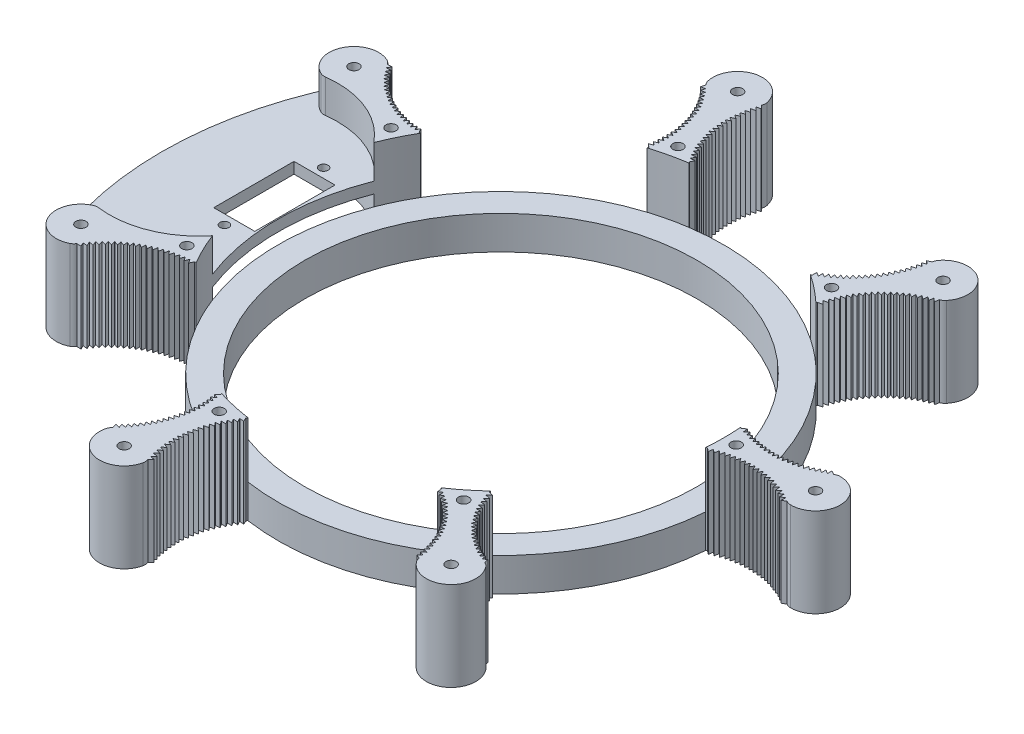
SolidWorks part; units mm, degrees
ref_plane "Front Plane" through (0, 0, 0) normal (0, 0, 1) x (1, 0, 0)
ref_plane "Top Plane" through (0, 0, 0) normal (0, 1, 0) x (1, 0, 0)
ref_plane "Right Plane" through (0, 0, 0) normal (1, 0, 0) x (0, 0, -1)
sketch "Sketch1" plane through (0, 0, 0) normal (0, 1, 0) x (1, 0, 0)
  circle A0 centre (0, 0) radius 63.5
  circle A1 centre (0, 0) radius 55.88
extrude "Boss-Extrude1" add sketch "Sketch1" along normal blind 9.525
sketch "Sketch2" plane through (0, 0, 0) normal (0, 1, 0) x (1, 0, 0)
  line L0 (0, 0) -> (143.528, 0) construction
  line L1 (0, 0) -> (106.3854, -8.3727) construction
  line L2 (88.1774, 6.6273) -> (87.0588, 7.2287)
  line L3 (87.0588, 7.2287) -> (87.0973, 5.9593)
  line L4 (87.0973, 5.9593) -> (88.1774, 6.6273) construction
  line L5 (87.086, 5.9526) -> (85.9991, 6.6097)
  line L6 (85.9991, 6.6097) -> (85.9735, 5.34)
  line L7 (85.9618, 5.3339) -> (84.9096, 6.045)
  line L8 (84.9096, 6.045) -> (84.8199, 4.7782)
  line L9 (84.8079, 4.7727) -> (83.7929, 5.5361)
  line L10 (83.7929, 5.5361) -> (83.6393, 4.2754)
  line L11 (83.6271, 4.2706) -> (82.652, 5.0842)
  line L12 (82.652, 5.0842) -> (82.4349, 3.8329)
  line L13 (82.4225, 3.8287) -> (81.4897, 4.6905)
  line L14 (81.4897, 4.6905) -> (81.2097, 3.4518)
  line L15 (81.197, 3.4482) -> (80.309, 4.356)
  line L16 (80.309, 4.356) -> (79.9668, 3.133)
  line L17 (79.954, 3.1301) -> (79.1129, 4.0816)
  line L18 (79.1129, 4.0816) -> (78.7094, 2.8774)
  line L19 (78.6964, 2.8751) -> (77.9044, 3.8679)
  line L20 (77.9044, 3.8679) -> (77.4406, 2.6856)
  line L21 (77.4276, 2.684) -> (76.6867, 3.7155)
  line L22 (76.6867, 3.7155) -> (76.1638, 2.5582)
  line L23 (76.1507, 2.5572) -> (75.4629, 3.6249)
  line L24 (75.4629, 3.6249) -> (74.8822, 2.4954)
  line L25 (74.8691, 2.4951) -> (74.2361, 3.5961)
  line L26 (74.2361, 3.5961) -> (73.5991, 2.4974)
  line L27 (73.586, 2.4977) -> (73.0094, 3.6293)
  line L28 (73.0094, 3.6293) -> (72.3177, 2.5642)
  line L29 (72.3046, 2.5652) -> (71.7859, 3.7244)
  line L30 (71.7859, 3.7244) -> (71.0413, 2.6956)
  line L31 (71.0283, 2.6973) -> (70.5688, 3.8812)
  line L32 (70.5688, 3.8812) -> (69.7732, 2.8913)
  line L33 (69.7602, 2.8936) -> (69.3611, 4.0993)
  line L34 (69.3611, 4.0993) -> (68.5165, 3.1508)
  line L35 (68.5037, 3.1538) -> (68.166, 4.3781)
  line L36 (68.166, 4.3781) -> (67.2746, 3.4734)
  line L37 (67.262, 3.4771) -> (66.9865, 4.7168)
  line L38 (66.9865, 4.7168) -> (66.0506, 3.8584)
  line L39 (66.0382, 3.8627) -> (65.8256, 5.1147)
  line L40 (65.8256, 5.1147) -> (64.8476, 4.3047)
  line L41 (64.8354, 4.3095) -> (64.6863, 5.5708)
  line L42 (64.6863, 5.5708) -> (63.6686, 4.8111)
  line L43 (88.1774, -6.6273) -> (87.0588, -7.2287)
  line L44 (87.0588, -7.2287) -> (87.0973, -5.9593)
  line L45 (87.086, -5.9526) -> (85.9991, -6.6097)
  line L46 (85.9991, -6.6097) -> (85.9735, -5.34)
  line L47 (85.9618, -5.3339) -> (84.9096, -6.045)
  line L48 (84.9096, -6.045) -> (84.8199, -4.7782)
  line L49 (84.8079, -4.7727) -> (83.7929, -5.5361)
  line L50 (83.7929, -5.5361) -> (83.6393, -4.2754)
  line L51 (83.6271, -4.2706) -> (82.652, -5.0842)
  line L52 (82.652, -5.0842) -> (82.4349, -3.8329)
  line L53 (82.4225, -3.8287) -> (81.4897, -4.6905)
  line L54 (81.4897, -4.6905) -> (81.2097, -3.4518)
  line L55 (81.197, -3.4482) -> (80.309, -4.356)
  line L56 (80.309, -4.356) -> (79.9668, -3.133)
  line L57 (79.954, -3.1301) -> (79.1129, -4.0816)
  line L58 (79.1129, -4.0816) -> (78.7094, -2.8774)
  line L59 (78.6964, -2.8751) -> (77.9044, -3.8679)
  line L60 (77.9044, -3.8679) -> (77.4406, -2.6856)
  line L61 (77.4276, -2.684) -> (76.6867, -3.7155)
  line L62 (76.6867, -3.7155) -> (76.1638, -2.5582)
  line L63 (76.1507, -2.5572) -> (75.4629, -3.6249)
  line L64 (75.4629, -3.6249) -> (74.8822, -2.4954)
  line L65 (74.8691, -2.4951) -> (74.2361, -3.5961)
  line L66 (74.2361, -3.5961) -> (73.5991, -2.4974)
  line L67 (73.586, -2.4977) -> (73.0094, -3.6293)
  line L68 (73.0094, -3.6293) -> (72.3177, -2.5642)
  line L69 (72.3046, -2.5652) -> (71.7859, -3.7244)
  line L70 (71.7859, -3.7244) -> (71.0413, -2.6956)
  line L71 (71.0283, -2.6973) -> (70.5688, -3.8812)
  line L72 (70.5688, -3.8812) -> (69.7732, -2.8913)
  line L73 (69.7602, -2.8936) -> (69.3611, -4.0993)
  line L74 (69.3611, -4.0993) -> (68.5165, -3.1508)
  line L75 (68.5037, -3.1538) -> (68.166, -4.3781)
  line L76 (68.166, -4.3781) -> (67.2746, -3.4734)
  line L77 (67.262, -3.4771) -> (66.9865, -4.7168)
  line L78 (66.9865, -4.7168) -> (66.0506, -3.8584)
  line L79 (66.0382, -3.8627) -> (65.8256, -5.1147)
  line L80 (65.8256, -5.1147) -> (64.8476, -4.3047)
  line L81 (64.8354, -4.3095) -> (64.6863, -5.5708)
  line L82 (64.6863, -5.5708) -> (63.6686, -4.8111)
  arc A0 (89.5346, -7.041) -> (89.5346, 7.041) centre (89.6247, 0) ccw
  arc A1 (63.3043, -4.9822) -> (88.1774, -6.6273) centre (74.2802, -27.8883) cw
  arc A2 (88.1774, 6.6273) -> (89.5346, 7.041) centre (89.5671, 4.5012) cw
  circle A3 centre (0, 0) radius 63.5 construction
  arc A4 (88.1774, -6.6273) -> (89.5346, -7.041) centre (89.5671, -4.5012) ccw
  arc A5 (63.3043, -4.9822) -> (63.2288, 5.8623) centre (0, 0) ccw
  arc A6 (63.3043, 4.9822) -> (88.1774, 6.6273) centre (74.2802, 27.8883) ccw
  circle A7 centre (89.6247, 0) radius 1.4605
  circle A8 centre (67.0187, 0) radius 1.4605
  point P13 (88.7043, -6.9812)
  point P84 (74.2802, 27.8883)
  dimension "D1" = 25.4
  dimension "D2" = 25.4
  dimension "D3" = 2.54
  dimension "D5" = 22.606
  dimension "D6" = 20
  dimension "D7" = 2.921
  dimension "D4" = 4.5
extrude "Boss-Extrude2" add sketch "Sketch2" along normal blind 25.4 contours A5 A6 A2 A0 A4 A1 region at (82.3063, 0, 0)
pattern_circular "CirPattern7" count 7 over 360 about axis through (0, 25.4, 0) along (0, -1, 0) of "Boss-Extrude2"
ref_plane "Plane1" through (0, 15.875, 0) normal (0, -1, 0) x (-1, 0, 0)
sketch "Sketch4" plane through (0, 15.875, 0) normal (0, -1, 0) x (-1, 0, 0)
  line L0 (0, 0) -> (125.7054, -60.5365) construction
  arc A7 (82.3206, 32.2877) -> (59.1968, 22.9779) centre (79.0244, 7.1025) ccw construction
  arc A14 (87.0934, 41.942) -> (87.0934, -41.942) centre (0, 0) cw
  arc A15 (83.7229, 32.5039) -> (77.6129, 45.1914) centre (80.7491, 38.8867) ccw construction
  arc A16 (82.3206, 32.2877) -> (83.7229, 32.5039) centre (82.6502, 34.8062) ccw construction
  arc A17 (59.1968, -22.9779) -> (59.1968, 22.9779) centre (0, 0) ccw construction
  arc A18 (59.1968, -22.9779) -> (82.3206, -32.2877) centre (79.0244, -7.1025) ccw construction
  arc A19 (77.6129, -45.1914) -> (83.7229, -32.5039) centre (80.7491, -38.8867) ccw construction
  arc A20 (83.7229, -32.5039) -> (82.3206, -32.2877) centre (82.6502, -34.8062) ccw construction
  arc A21 (82.3206, 32.2877) -> (59.1968, 22.9779) centre (79.0244, 7.1025) ccw
  arc A22 (83.7229, 32.5039) -> (87.0934, 41.942) centre (80.7491, 38.8867) ccw
  arc A23 (82.3206, 32.2877) -> (83.7229, 32.5039) centre (82.6502, 34.8062) ccw
  arc A24 (59.1968, -22.9779) -> (59.1968, 22.9779) centre (0, 0) ccw
  arc A25 (59.1968, -22.9779) -> (82.3206, -32.2877) centre (79.0244, -7.1025) ccw
  arc A26 (87.0934, -41.942) -> (83.7229, -32.5039) centre (80.7491, -38.8867) ccw
  arc A27 (83.7229, -32.5039) -> (82.3206, -32.2877) centre (82.6502, -34.8062) ccw
extrude "Boss-Extrude3" add sketch "Sketch4" along normal blind 3.175
sketch "Sketch5" plane through (0, 12.7, 0) normal (0, -1, 0) x (-1, 0, 0)
  line L0 (59.1968, -22.9779) -> (59.1968, 22.9779) construction
  line L1 (59.1968, 0) -> (63.7688, 0) construction
  line L2 (63.7688, 0) -> (63.7688, -6.35)
  line L3 (63.7688, -6.35) -> (75.4528, -6.35)
  line L4 (75.4528, -6.35) -> (75.4528, 16.51)
  line L5 (75.4528, 16.51) -> (63.7688, 16.51)
  line L6 (63.7688, 16.51) -> (63.7688, 0)
extrude "Cut-Extrude1" cut sketch "Sketch5" against normal through all
sketch "Sketch6" plane through (0, 12.7, 0) normal (0, -1, 0) x (1, 0, 0)
  circle A0 centre (-69.6743, -19.1516) radius 1.27
extrude "Cut-Extrude2" cut sketch "Sketch6" against normal up to surface (3.175 mm away) up to face at (-69.6108, 15.875, -5.08)
sketch "Sketch7" plane through (0, 12.7, 0) normal (0, -1, 0) x (1, 0, 0)
  circle A0 centre (-69.6743, 9.0932) radius 1.27
extrude "Cut-Extrude3" cut sketch "Sketch7" against normal up to surface (3.175 mm away) up to face at (-69.6743, 15.875, -20.4216)
extrude "Boss-Extrude4" add sketch "Sketch2<4>" along normal up to surface (25.4 mm away) contours A6 L42 L41 region at (64.3954, 0, -4.8939) up to face at (89.6247, 25.4, -1.4605)
sketch "Sketch2<4>" plane through (0, 0, 0) normal (0, 1, 0) x (1, 0, 0) same geometry as "Sketch2"
extrude "Boss-Extrude5" add sketch "Sketch2<5>" along normal up to surface (25.4 mm away) contours L82 A1 L81 region at (64.3954, 0, 4.8939) up to face at (89.6247, 25.4, -1.4605)
sketch "Sketch2<5>" plane through (0, 0, 0) normal (0, 1, 0) x (1, 0, 0) same geometry as "Sketch2"
pattern_circular "CirPattern2" count 20 over 55 about axis through (74.2802, 25.4, 27.8883) along (0, -1, 0) of "Boss-Extrude5"
pattern_circular "CirPattern3" count 20 over 55 about axis through (74.2802, 25.4, -27.8883) along (0, -1, 0) of "Boss-Extrude4" reverse direction yes
pattern_circular "CirPattern4" count 7 over 360 about axis through (0, 25.4, 0) along (0, -1, 0) skipping 4 of "CirPattern3"
pattern_circular "CirPattern5" count 7 over 360 about axis through (0, 9.525, 0) along (0, -1, 0) skipping 3 of "CirPattern2"
sketch "Sketch11" plane through (0, 15.875, 0) normal (0, 1, 0) x (1, 0, 0)
  line L0 (-55.276, 31.9594) -> (-55.8633, 33.0854) construction
  line L1 (-55.8633, 33.0854) -> (-56.5448, 32.0138) construction
  line L2 (-56.5448, 32.0138) -> (-56.5579, 32.0147) construction
  line L3 (-56.5579, 32.0147) -> (-57.0877, 33.1689) construction
  line L4 (-57.0877, 33.1689) -> (-57.8224, 32.133) construction
  line L5 (-57.8224, 32.133) -> (-57.8354, 32.1346) construction
  line L6 (-57.8354, 32.1346) -> (-58.3062, 33.3141) construction
  line L7 (-58.3062, 33.3141) -> (-59.0923, 32.3166) construction
  line L8 (-59.0923, 32.3166) -> (-59.1053, 32.3188) construction
  line L9 (-59.1053, 32.3188) -> (-59.5159, 33.5206) construction
  line L10 (-59.5159, 33.5206) -> (-60.3514, 32.5641) construction
  line L11 (-60.3514, 32.5641) -> (-60.3642, 32.567) construction
  line L12 (-60.3642, 32.567) -> (-60.7136, 33.788) construction
  line L13 (-60.7136, 33.788) -> (-61.5963, 32.8749) construction
  line L14 (-61.5963, 32.8749) -> (-61.609, 32.8784) construction
  line L15 (-61.609, 32.8784) -> (-61.8962, 34.1155) construction
  line L16 (-61.8962, 34.1155) -> (-62.8239, 33.2482) construction
  line L17 (-62.8239, 33.2482) -> (-62.8364, 33.2523) construction
  line L18 (-62.8364, 33.2523) -> (-63.0609, 34.5023) construction
  line L19 (-63.0609, 34.5023) -> (-64.0312, 33.6829) construction
  line L20 (-64.0312, 33.6829) -> (-64.0434, 33.6877) construction
  line L21 (-64.0434, 33.6877) -> (-64.2045, 34.9475) construction
  line L22 (-64.2045, 34.9475) -> (-65.2149, 34.1781) construction
  line L23 (-65.2149, 34.1781) -> (-65.2269, 34.1835) construction
  line L24 (-65.2269, 34.1835) -> (-65.3241, 35.4498) construction
  line L25 (-65.3241, 35.4498) -> (-66.3721, 34.7325) construction
  line L26 (-66.3721, 34.7325) -> (-66.3839, 34.7384) construction
  line L27 (-66.3839, 34.7384) -> (-66.417, 36.008) construction
  line L28 (-66.417, 36.008) -> (-67.4999, 35.3445) construction
  line L29 (-67.4999, 35.3445) -> (-67.5113, 35.3511) construction
  line L30 (-67.5113, 35.3511) -> (-67.4803, 36.6207) construction
  line L31 (-67.4803, 36.6207) -> (-68.5953, 36.0128) construction
  line L32 (-68.5953, 36.0128) -> (-68.6063, 36.0199) construction
  line L33 (-68.6063, 36.0199) -> (-68.5112, 37.2863) construction
  line L34 (-68.5112, 37.2863) -> (-69.6556, 36.7355) construction
  line L35 (-69.6556, 36.7355) -> (-69.6662, 36.7432) construction
  line L36 (-69.6662, 36.7432) -> (-69.5073, 38.0032) construction
  line L37 (-69.5073, 38.0032) -> (-70.678, 37.5108) construction
  line L38 (-70.678, 37.5108) -> (-70.6882, 37.519) construction
  line L39 (-70.6882, 37.519) -> (-70.4659, 38.7694) construction
  line L40 (-70.4659, 38.7694) -> (-71.6599, 38.3368) construction
  line L41 (-71.6599, 38.3368) -> (-71.6697, 38.3455) construction
  line L42 (-71.6697, 38.3455) -> (-71.3845, 39.5831) construction
  line L43 (-71.3845, 39.5831) -> (-72.5989, 39.2113) construction
  line L44 (-72.5989, 39.2113) -> (-72.6083, 39.2205) construction
  line L45 (-72.6083, 39.2205) -> (-72.2609, 40.4421) construction
  line L46 (-72.2609, 40.4421) -> (-73.4925, 40.1321) construction
  line L47 (-73.4925, 40.1321) -> (-73.5014, 40.1418) construction
  line L48 (-73.5014, 40.1418) -> (-73.0928, 41.3442) construction
  line L49 (-73.0928, 41.3442) -> (-74.3385, 41.0969) construction
  line L50 (-74.3385, 41.0969) -> (-74.3469, 41.107) construction
  line L51 (-74.3469, 41.107) -> (-73.8781, 42.2873) construction
  line L52 (-73.8781, 42.2873) -> (-75.1346, 42.1031) construction
  line L53 (-75.1346, 42.1031) -> (-75.1425, 42.1136) construction
  line L54 (-75.1425, 42.1136) -> (-74.6147, 43.2688) construction
  line L55 (-74.6147, 43.2688) -> (-75.879, 43.1483) construction
  line L56 (-75.879, 43.1483) -> (-75.8863, 43.1592) construction
  line L57 (-75.8863, 43.1592) -> (-75.3009, 44.2862) construction
  line L58 (-75.3009, 44.2862) -> (-76.5696, 44.2297) construction
  line L59 (-76.5696, -44.2297) -> (-75.3009, -44.2862) construction
  line L60 (-75.3009, -44.2862) -> (-75.8863, -43.1592) construction
  line L61 (-75.8863, -43.1592) -> (-75.879, -43.1483) construction
  line L62 (-75.879, -43.1483) -> (-74.6147, -43.2688) construction
  line L63 (-74.6147, -43.2688) -> (-75.1425, -42.1136) construction
  line L64 (-75.1425, -42.1136) -> (-75.1346, -42.1031) construction
  line L65 (-75.1346, -42.1031) -> (-73.8781, -42.2873) construction
  line L66 (-73.8781, -42.2873) -> (-74.3469, -41.107) construction
  line L67 (-74.3469, -41.107) -> (-74.3385, -41.0969) construction
  line L68 (-74.3385, -41.0969) -> (-73.0928, -41.3442) construction
  line L69 (-73.0928, -41.3442) -> (-73.5014, -40.1418) construction
  line L70 (-73.5014, -40.1418) -> (-73.4925, -40.1321) construction
  line L71 (-73.4925, -40.1321) -> (-72.2609, -40.4421) construction
  line L72 (-72.2609, -40.4421) -> (-72.6083, -39.2205) construction
  line L73 (-72.6083, -39.2205) -> (-72.5989, -39.2113) construction
  line L74 (-72.5989, -39.2113) -> (-71.3845, -39.5831) construction
  line L75 (-71.3845, -39.5831) -> (-71.6697, -38.3455) construction
  line L76 (-71.6697, -38.3455) -> (-71.6599, -38.3368) construction
  line L77 (-71.6599, -38.3368) -> (-70.4659, -38.7694) construction
  line L78 (-70.4659, -38.7694) -> (-70.6882, -37.519) construction
  line L79 (-70.6882, -37.519) -> (-70.678, -37.5108) construction
  line L80 (-70.678, -37.5108) -> (-69.5073, -38.0032) construction
  line L81 (-69.5073, -38.0032) -> (-69.6662, -36.7432) construction
  line L82 (-69.6662, -36.7432) -> (-69.6556, -36.7355) construction
  line L83 (-69.6556, -36.7355) -> (-68.5112, -37.2863) construction
  line L84 (-68.5112, -37.2863) -> (-68.6063, -36.0199) construction
  line L85 (-68.6063, -36.0199) -> (-68.5953, -36.0128) construction
  line L86 (-68.5953, -36.0128) -> (-67.4803, -36.6207) construction
  line L87 (-67.4803, -36.6207) -> (-67.5113, -35.3511) construction
  line L88 (-67.5113, -35.3511) -> (-67.4999, -35.3445) construction
  line L89 (-67.4999, -35.3445) -> (-66.417, -36.008) construction
  line L90 (-66.417, -36.008) -> (-66.3839, -34.7384) construction
  line L91 (-66.3839, -34.7384) -> (-66.3721, -34.7325) construction
  line L92 (-66.3721, -34.7325) -> (-65.3241, -35.4498) construction
  line L93 (-65.3241, -35.4498) -> (-65.2269, -34.1835) construction
  line L94 (-65.2269, -34.1835) -> (-65.2149, -34.1781) construction
  line L95 (-65.2149, -34.1781) -> (-64.2045, -34.9475) construction
  line L96 (-64.2045, -34.9475) -> (-64.0434, -33.6877) construction
  line L97 (-64.0434, -33.6877) -> (-64.0312, -33.6829) construction
  line L98 (-64.0312, -33.6829) -> (-63.0609, -34.5023) construction
  line L99 (-63.0609, -34.5023) -> (-62.8364, -33.2523) construction
  line L100 (-62.8364, -33.2523) -> (-62.8239, -33.2482) construction
  line L101 (-62.8239, -33.2482) -> (-61.8962, -34.1155) construction
  line L102 (-61.8962, -34.1155) -> (-61.609, -32.8784) construction
  line L103 (-61.609, -32.8784) -> (-61.5963, -32.8749) construction
  line L104 (-61.5963, -32.8749) -> (-60.7136, -33.788) construction
  line L105 (-60.7136, -33.788) -> (-60.3642, -32.567) construction
  line L106 (-60.3642, -32.567) -> (-60.3514, -32.5641) construction
  line L107 (-60.3514, -32.5641) -> (-59.5159, -33.5206) construction
  line L108 (-59.5159, -33.5206) -> (-59.1053, -32.3188) construction
  line L109 (-59.1053, -32.3188) -> (-59.0923, -32.3166) construction
  line L110 (-59.0923, -32.3166) -> (-58.3062, -33.3141) construction
  line L111 (-58.3062, -33.3141) -> (-57.8354, -32.1346) construction
  line L112 (-57.8354, -32.1346) -> (-57.8224, -32.133) construction
  line L113 (-57.8224, -32.133) -> (-57.0877, -33.1689) construction
  line L114 (-57.0877, -33.1689) -> (-56.5579, -32.0147) construction
  line L115 (-56.5579, -32.0147) -> (-56.5448, -32.0138) construction
  line L116 (-56.5448, -32.0138) -> (-55.8633, -33.0854) construction
  line L117 (-55.8633, -33.0854) -> (-55.276, -31.9594) construction
  line L118 (-55.276, 31.9594) -> (-55.8633, 33.0854)
  line L119 (-55.8633, 33.0854) -> (-56.5448, 32.0138)
  line L120 (-56.5448, 32.0138) -> (-56.5579, 32.0147)
  line L121 (-56.5579, 32.0147) -> (-57.0877, 33.1689)
  line L122 (-57.0877, 33.1689) -> (-57.8224, 32.133)
  line L123 (-57.8224, 32.133) -> (-57.8354, 32.1346)
  line L124 (-57.8354, 32.1346) -> (-58.3062, 33.3141)
  line L125 (-58.3062, 33.3141) -> (-59.0923, 32.3166)
  line L126 (-59.0923, 32.3166) -> (-59.1053, 32.3188)
  line L127 (-59.1053, 32.3188) -> (-59.5159, 33.5206)
  line L128 (-59.5159, 33.5206) -> (-60.3514, 32.5641)
  line L129 (-60.3514, 32.5641) -> (-60.3642, 32.567)
  line L130 (-60.3642, 32.567) -> (-60.7136, 33.788)
  line L131 (-60.7136, 33.788) -> (-61.5963, 32.8749)
  line L132 (-61.5963, 32.8749) -> (-61.609, 32.8784)
  line L133 (-61.609, 32.8784) -> (-61.8962, 34.1155)
  line L134 (-61.8962, 34.1155) -> (-62.8239, 33.2482)
  line L135 (-62.8239, 33.2482) -> (-62.8364, 33.2523)
  line L136 (-62.8364, 33.2523) -> (-63.0609, 34.5023)
  line L137 (-63.0609, 34.5023) -> (-64.0312, 33.6829)
  line L138 (-64.0312, 33.6829) -> (-64.0434, 33.6877)
  line L139 (-64.0434, 33.6877) -> (-64.2045, 34.9475)
  line L140 (-64.2045, 34.9475) -> (-65.2149, 34.1781)
  line L141 (-65.2149, 34.1781) -> (-65.2269, 34.1835)
  line L142 (-65.2269, 34.1835) -> (-65.3241, 35.4498)
  line L143 (-65.3241, 35.4498) -> (-66.3721, 34.7325)
  line L144 (-66.3721, 34.7325) -> (-66.3839, 34.7384)
  line L145 (-66.3839, 34.7384) -> (-66.417, 36.008)
  line L146 (-66.417, 36.008) -> (-67.4999, 35.3445)
  line L147 (-67.4999, 35.3445) -> (-67.5113, 35.3511)
  line L148 (-67.5113, 35.3511) -> (-67.4803, 36.6207)
  line L149 (-67.4803, 36.6207) -> (-68.5953, 36.0128)
  line L150 (-68.5953, 36.0128) -> (-68.6063, 36.0199)
  line L151 (-68.6063, 36.0199) -> (-68.5112, 37.2863)
  line L152 (-68.5112, 37.2863) -> (-69.6556, 36.7355)
  line L153 (-69.6556, 36.7355) -> (-69.6662, 36.7432)
  line L154 (-69.6662, 36.7432) -> (-69.5073, 38.0032)
  line L155 (-69.5073, 38.0032) -> (-70.678, 37.5108)
  line L156 (-70.678, 37.5108) -> (-70.6882, 37.519)
  line L157 (-70.6882, 37.519) -> (-70.4659, 38.7694)
  line L158 (-70.4659, 38.7694) -> (-71.6599, 38.3368)
  line L159 (-71.6599, 38.3368) -> (-71.6697, 38.3455)
  line L160 (-71.6697, 38.3455) -> (-71.3845, 39.5831)
  line L161 (-71.3845, 39.5831) -> (-72.5989, 39.2113)
  line L162 (-72.5989, 39.2113) -> (-72.6083, 39.2205)
  line L163 (-72.6083, 39.2205) -> (-72.2609, 40.4421)
  line L164 (-72.2609, 40.4421) -> (-73.4925, 40.1321)
  line L165 (-73.4925, 40.1321) -> (-73.5014, 40.1418)
  line L166 (-73.5014, 40.1418) -> (-73.0928, 41.3442)
  line L167 (-73.0928, 41.3442) -> (-74.3385, 41.0969)
  line L168 (-74.3385, 41.0969) -> (-74.3469, 41.107)
  line L169 (-74.3469, 41.107) -> (-73.8781, 42.2873)
  line L170 (-73.8781, 42.2873) -> (-75.1346, 42.1031)
  line L171 (-75.1346, 42.1031) -> (-75.1425, 42.1136)
  line L172 (-75.1425, 42.1136) -> (-74.6147, 43.2688)
  line L173 (-74.6147, 43.2688) -> (-75.879, 43.1483)
  line L174 (-75.879, 43.1483) -> (-75.8863, 43.1592)
  line L175 (-75.8863, 43.1592) -> (-75.3009, 44.2862)
  line L176 (-75.3009, 44.2862) -> (-76.5696, 44.2297)
  line L177 (-76.5696, -44.2297) -> (-75.3009, -44.2862)
  line L178 (-75.3009, -44.2862) -> (-75.8863, -43.1592)
  line L179 (-75.8863, -43.1592) -> (-75.879, -43.1483)
  line L180 (-75.879, -43.1483) -> (-74.6147, -43.2688)
  line L181 (-74.6147, -43.2688) -> (-75.1425, -42.1136)
  line L182 (-75.1425, -42.1136) -> (-75.1346, -42.1031)
  line L183 (-75.1346, -42.1031) -> (-73.8781, -42.2873)
  line L184 (-73.8781, -42.2873) -> (-74.3469, -41.107)
  line L185 (-74.3469, -41.107) -> (-74.3385, -41.0969)
  line L186 (-74.3385, -41.0969) -> (-73.0928, -41.3442)
  line L187 (-73.0928, -41.3442) -> (-73.5014, -40.1418)
  line L188 (-73.5014, -40.1418) -> (-73.4925, -40.1321)
  line L189 (-73.4925, -40.1321) -> (-72.2609, -40.4421)
  line L190 (-72.2609, -40.4421) -> (-72.6083, -39.2205)
  line L191 (-72.6083, -39.2205) -> (-72.5989, -39.2113)
  line L192 (-72.5989, -39.2113) -> (-71.3845, -39.5831)
  line L193 (-71.3845, -39.5831) -> (-71.6697, -38.3455)
  line L194 (-71.6697, -38.3455) -> (-71.6599, -38.3368)
  line L195 (-71.6599, -38.3368) -> (-70.4659, -38.7694)
  line L196 (-70.4659, -38.7694) -> (-70.6882, -37.519)
  line L197 (-70.6882, -37.519) -> (-70.678, -37.5108)
  line L198 (-70.678, -37.5108) -> (-69.5073, -38.0032)
  line L199 (-69.5073, -38.0032) -> (-69.6662, -36.7432)
  line L200 (-69.6662, -36.7432) -> (-69.6556, -36.7355)
  line L201 (-69.6556, -36.7355) -> (-68.5112, -37.2863)
  line L202 (-68.5112, -37.2863) -> (-68.6063, -36.0199)
  line L203 (-68.6063, -36.0199) -> (-68.5953, -36.0128)
  line L204 (-68.5953, -36.0128) -> (-67.4803, -36.6207)
  line L205 (-67.4803, -36.6207) -> (-67.5113, -35.3511)
  line L206 (-67.5113, -35.3511) -> (-67.4999, -35.3445)
  line L207 (-67.4999, -35.3445) -> (-66.417, -36.008)
  line L208 (-66.417, -36.008) -> (-66.3839, -34.7384)
  line L209 (-66.3839, -34.7384) -> (-66.3721, -34.7325)
  line L210 (-66.3721, -34.7325) -> (-65.3241, -35.4498)
  line L211 (-65.3241, -35.4498) -> (-65.2269, -34.1835)
  line L212 (-65.2269, -34.1835) -> (-65.2149, -34.1781)
  line L213 (-65.2149, -34.1781) -> (-64.2045, -34.9475)
  line L214 (-64.2045, -34.9475) -> (-64.0434, -33.6877)
  line L215 (-64.0434, -33.6877) -> (-64.0312, -33.6829)
  line L216 (-64.0312, -33.6829) -> (-63.0609, -34.5023)
  line L217 (-63.0609, -34.5023) -> (-62.8364, -33.2523)
  line L218 (-62.8364, -33.2523) -> (-62.8239, -33.2482)
  line L219 (-62.8239, -33.2482) -> (-61.8962, -34.1155)
  line L220 (-61.8962, -34.1155) -> (-61.609, -32.8784)
  line L221 (-61.609, -32.8784) -> (-61.5963, -32.8749)
  line L222 (-61.5963, -32.8749) -> (-60.7136, -33.788)
  line L223 (-60.7136, -33.788) -> (-60.3642, -32.567)
  line L224 (-60.3642, -32.567) -> (-60.3514, -32.5641)
  line L225 (-60.3514, -32.5641) -> (-59.5159, -33.5206)
  line L226 (-59.5159, -33.5206) -> (-59.1053, -32.3188)
  line L227 (-59.1053, -32.3188) -> (-59.0923, -32.3166)
  line L228 (-59.0923, -32.3166) -> (-58.3062, -33.3141)
  line L229 (-58.3062, -33.3141) -> (-57.8354, -32.1346)
  line L230 (-57.8354, -32.1346) -> (-57.8224, -32.133)
  line L231 (-57.8224, -32.133) -> (-57.0877, -33.1689)
  line L232 (-57.0877, -33.1689) -> (-56.5579, -32.0147)
  line L233 (-56.5579, -32.0147) -> (-56.5448, -32.0138)
  line L234 (-56.5448, -32.0138) -> (-55.8633, -33.0854)
  line L235 (-55.8633, -33.0854) -> (-55.276, -31.9594)
  arc A0 (-54.8735, 31.9554) -> (-59.1968, 22.9779) centre (0, 0) ccw construction
  arc A1 (-55.276, 31.9594) -> (-54.8735, 31.9554) centre (-54.8239, 57.3554) ccw construction
  arc A2 (-76.5696, 44.2297) -> (-77.6129, 45.1914) centre (-78.7442, 42.9172) ccw construction
  arc A3 (-77.6129, 45.1914) -> (-83.7229, 32.5039) centre (-80.7491, 38.8867) ccw construction
  arc A6 (-59.1968, -22.9779) -> (-54.8735, -31.9554) centre (0, 0) ccw construction
  arc A9 (-83.7229, -32.5039) -> (-77.6129, -45.1914) centre (-80.7491, -38.8867) ccw construction
  arc A10 (-77.6129, -45.1914) -> (-76.5696, -44.2297) centre (-78.7442, -42.9172) ccw construction
  arc A11 (-54.8735, -31.9554) -> (-55.276, -31.9594) centre (-54.8239, -57.3554) ccw construction
  arc A12 (-87.0934, 41.942) -> (-87.0934, -41.942) centre (0, 0) ccw construction
  arc A13 (-59.1968, 22.9779) -> (-59.1968, -22.9779) centre (0, 0) ccw construction
  arc A14 (-54.8735, 31.9554) -> (-59.1968, 22.9779) centre (0, 0) ccw
  arc A15 (-55.276, 31.9594) -> (-54.8735, 31.9554) centre (-54.8239, 57.3554) ccw
  arc A16 (-76.5696, 44.2297) -> (-77.6129, 45.1914) centre (-78.7442, 42.9172) ccw
  arc A17 (-77.6129, 45.1914) -> (-87.0934, 41.942) centre (-80.7491, 38.8867) ccw
  arc A20 (-59.1968, -22.9779) -> (-54.8735, -31.9554) centre (0, 0) ccw
  arc A23 (-87.0934, -41.942) -> (-77.6129, -45.1914) centre (-80.7491, -38.8867) ccw
  arc A24 (-77.6129, -45.1914) -> (-76.5696, -44.2297) centre (-78.7442, -42.9172) ccw
  arc A25 (-54.8735, -31.9554) -> (-55.276, -31.9594) centre (-54.8239, -57.3554) ccw
  arc A26 (-87.0934, 41.942) -> (-87.0934, -41.942) centre (0, 0) ccw
  arc A27 (-59.1968, 22.9779) -> (-59.1968, -22.9779) centre (0, 0) ccw
extrude "Cut-Extrude8" [suppressed] cut sketch "Sketch11" against normal through all flip side to cut
sketch "Sketch12" [suppressed] plane through (0, 15.875, 0) normal (0, 1, 0) x (1, 0, 0)
  line L0 (-63.7688, 16.51) -> (-61.3161, 16.51)
  line L1 (-63.7688, -6.35) -> (-63.1817, -6.35)
  line L4 (-75.4528, 16.51) -> (-75.4528, -6.35)
  line L5 (-63.7688, 16.51) -> (-75.4528, 16.51)
  line L6 (-63.7688, -6.35) -> (-63.7688, 16.51)
  line L7 (-75.4528, -6.35) -> (-63.7688, -6.35)
  line L8 (-75.4528, 16.51) -> (-75.4528, -6.35)
  line L9 (-63.7688, 16.51) -> (-75.4528, 16.51)
  line L11 (-75.4528, -6.35) -> (-63.7688, -6.35)
  line L67 (-55.276, 31.9594) -> (-55.8633, 33.0854)
  line L68 (-55.8633, 33.0854) -> (-56.5448, 32.0138)
  line L69 (-56.5448, 32.0138) -> (-56.5579, 32.0147)
  line L70 (-56.5579, 32.0147) -> (-57.0877, 33.1689)
  line L71 (-57.0877, 33.1689) -> (-57.8224, 32.133)
  line L72 (-57.8224, 32.133) -> (-57.8354, 32.1346)
  line L73 (-57.8354, 32.1346) -> (-58.3062, 33.3141)
  line L74 (-58.3062, 33.3141) -> (-59.0923, 32.3166)
  line L75 (-59.0923, 32.3166) -> (-59.1053, 32.3188)
  line L76 (-59.1053, 32.3188) -> (-59.5159, 33.5206)
  line L77 (-59.5159, 33.5206) -> (-60.3514, 32.5641)
  line L78 (-60.3514, 32.5641) -> (-60.3642, 32.567)
  line L79 (-60.3642, 32.567) -> (-60.7136, 33.788)
  line L80 (-60.7136, 33.788) -> (-61.5963, 32.8749)
  line L81 (-61.5963, 32.8749) -> (-61.609, 32.8784)
  line L82 (-61.609, 32.8784) -> (-61.8962, 34.1155)
  line L83 (-61.8962, 34.1155) -> (-62.8239, 33.2482)
  line L84 (-62.8239, 33.2482) -> (-62.8364, 33.2523)
  line L85 (-62.8364, 33.2523) -> (-63.0609, 34.5023)
  line L86 (-63.0609, 34.5023) -> (-64.0312, 33.6829)
  line L87 (-64.0312, 33.6829) -> (-64.0434, 33.6877)
  line L88 (-64.0434, 33.6877) -> (-64.2045, 34.9475)
  line L89 (-64.2045, 34.9475) -> (-65.2149, 34.1781)
  line L90 (-65.2149, 34.1781) -> (-65.2269, 34.1835)
  line L91 (-65.2269, 34.1835) -> (-65.3241, 35.4498)
  line L92 (-65.3241, 35.4498) -> (-66.3721, 34.7325)
  line L93 (-66.3721, 34.7325) -> (-66.3839, 34.7384)
  line L94 (-66.3839, 34.7384) -> (-66.417, 36.008)
  line L95 (-66.417, 36.008) -> (-67.4999, 35.3445)
  line L96 (-67.4999, 35.3445) -> (-67.5113, 35.3511)
  line L97 (-67.5113, 35.3511) -> (-67.4803, 36.6207)
  line L98 (-67.4803, 36.6207) -> (-68.5953, 36.0128)
  line L99 (-68.5953, 36.0128) -> (-68.6063, 36.0199)
  line L100 (-68.6063, 36.0199) -> (-68.5112, 37.2863)
  line L101 (-68.5112, 37.2863) -> (-69.6556, 36.7355)
  line L102 (-69.6556, 36.7355) -> (-69.6662, 36.7432)
  line L103 (-69.6662, 36.7432) -> (-69.5073, 38.0032)
  line L104 (-69.5073, 38.0032) -> (-70.678, 37.5108)
  line L105 (-70.678, 37.5108) -> (-70.6882, 37.519)
  line L106 (-70.6882, 37.519) -> (-70.4659, 38.7694)
  line L107 (-70.4659, 38.7694) -> (-71.6599, 38.3368)
  line L108 (-71.6599, 38.3368) -> (-71.6697, 38.3455)
  line L109 (-71.6697, 38.3455) -> (-71.3845, 39.5831)
  line L110 (-71.3845, 39.5831) -> (-72.5989, 39.2113)
  line L111 (-72.5989, 39.2113) -> (-72.6083, 39.2205)
  line L112 (-72.6083, 39.2205) -> (-72.2609, 40.4421)
  line L113 (-72.2609, 40.4421) -> (-73.4925, 40.1321)
  line L114 (-73.4925, 40.1321) -> (-73.5014, 40.1418)
  line L115 (-73.5014, 40.1418) -> (-73.0928, 41.3442)
  line L116 (-73.0928, 41.3442) -> (-74.3385, 41.0969)
  line L117 (-74.3385, 41.0969) -> (-74.3469, 41.107)
  line L118 (-74.3469, 41.107) -> (-73.8781, 42.2873)
  line L119 (-73.8781, 42.2873) -> (-75.1346, 42.1031)
  line L120 (-75.1346, 42.1031) -> (-75.1425, 42.1136)
  line L121 (-75.1425, 42.1136) -> (-74.6147, 43.2688)
  line L122 (-74.6147, 43.2688) -> (-75.879, 43.1483)
  line L123 (-75.879, 43.1483) -> (-75.8863, 43.1592)
  line L124 (-75.8863, 43.1592) -> (-75.3009, 44.2862)
  line L125 (-75.3009, 44.2862) -> (-76.5696, 44.2297)
  line L126 (-55.276, 31.9594) -> (-55.8633, 33.0854)
  line L127 (-55.8633, 33.0854) -> (-56.5448, 32.0138)
  line L128 (-56.5448, 32.0138) -> (-56.5579, 32.0147)
  line L129 (-56.5579, 32.0147) -> (-57.0877, 33.1689)
  line L130 (-57.0877, 33.1689) -> (-57.8224, 32.133)
  line L131 (-57.8224, 32.133) -> (-57.8354, 32.1346)
  line L132 (-57.8354, 32.1346) -> (-58.3062, 33.3141)
  line L133 (-58.3062, 33.3141) -> (-59.0923, 32.3166)
  line L134 (-59.0923, 32.3166) -> (-59.1053, 32.3188)
  line L135 (-59.1053, 32.3188) -> (-59.5159, 33.5206)
  line L136 (-59.5159, 33.5206) -> (-60.3514, 32.5641)
  line L137 (-60.3514, 32.5641) -> (-60.3642, 32.567)
  line L138 (-60.3642, 32.567) -> (-60.7136, 33.788)
  line L139 (-60.7136, 33.788) -> (-61.5963, 32.8749)
  line L140 (-61.5963, 32.8749) -> (-61.609, 32.8784)
  line L141 (-61.609, 32.8784) -> (-61.8962, 34.1155)
  line L142 (-61.8962, 34.1155) -> (-62.8239, 33.2482)
  line L143 (-62.8239, 33.2482) -> (-62.8364, 33.2523)
  line L144 (-62.8364, 33.2523) -> (-63.0609, 34.5023)
  line L145 (-63.0609, 34.5023) -> (-64.0312, 33.6829)
  line L146 (-64.0312, 33.6829) -> (-64.0434, 33.6877)
  line L147 (-64.0434, 33.6877) -> (-64.2045, 34.9475)
  line L148 (-64.2045, 34.9475) -> (-65.2149, 34.1781)
  line L149 (-65.2149, 34.1781) -> (-65.2269, 34.1835)
  line L150 (-65.2269, 34.1835) -> (-65.3241, 35.4498)
  line L151 (-65.3241, 35.4498) -> (-66.3721, 34.7325)
  line L152 (-66.3721, 34.7325) -> (-66.3839, 34.7384)
  line L153 (-66.3839, 34.7384) -> (-66.417, 36.008)
  line L154 (-66.417, 36.008) -> (-67.4999, 35.3445)
  line L155 (-67.4999, 35.3445) -> (-67.5113, 35.3511)
  line L156 (-67.5113, 35.3511) -> (-67.4803, 36.6207)
  line L157 (-67.4803, 36.6207) -> (-68.5953, 36.0128)
  line L158 (-68.5953, 36.0128) -> (-68.6063, 36.0199)
  line L159 (-68.6063, 36.0199) -> (-68.5112, 37.2863)
  line L160 (-68.5112, 37.2863) -> (-69.6556, 36.7355)
  line L161 (-69.6556, 36.7355) -> (-69.6662, 36.7432)
  line L162 (-69.6662, 36.7432) -> (-69.5073, 38.0032)
  line L163 (-69.5073, 38.0032) -> (-70.678, 37.5108)
  line L164 (-70.678, 37.5108) -> (-70.6882, 37.519)
  line L165 (-70.6882, 37.519) -> (-70.4659, 38.7694)
  line L166 (-70.4659, 38.7694) -> (-71.6599, 38.3368)
  line L167 (-71.6599, 38.3368) -> (-71.6697, 38.3455)
  line L168 (-71.6697, 38.3455) -> (-71.3845, 39.5831)
  line L169 (-71.3845, 39.5831) -> (-72.5989, 39.2113)
  line L170 (-72.5989, 39.2113) -> (-72.6083, 39.2205)
  line L171 (-72.6083, 39.2205) -> (-72.2609, 40.4421)
  line L172 (-72.2609, 40.4421) -> (-73.4925, 40.1321)
  line L173 (-73.4925, 40.1321) -> (-73.5014, 40.1418)
  line L174 (-73.5014, 40.1418) -> (-73.0928, 41.3442)
  line L175 (-73.0928, 41.3442) -> (-74.3385, 41.0969)
  line L176 (-74.3385, 41.0969) -> (-74.3469, 41.107)
  line L177 (-74.3469, 41.107) -> (-73.8781, 42.2873)
  line L178 (-73.8781, 42.2873) -> (-75.1346, 42.1031)
  line L179 (-75.1346, 42.1031) -> (-75.1425, 42.1136)
  line L180 (-75.1425, 42.1136) -> (-74.6147, 43.2688)
  line L181 (-74.6147, 43.2688) -> (-75.879, 43.1483)
  line L182 (-75.879, 43.1483) -> (-75.8863, 43.1592)
  line L183 (-75.8863, 43.1592) -> (-75.3009, 44.2862)
  line L184 (-75.3009, 44.2862) -> (-76.5696, 44.2297)
  line L185 (-76.5696, -44.2297) -> (-75.3009, -44.2862)
  line L186 (-75.3009, -44.2862) -> (-75.8863, -43.1592)
  line L187 (-75.8863, -43.1592) -> (-75.879, -43.1483)
  line L188 (-75.879, -43.1483) -> (-74.6147, -43.2688)
  line L189 (-74.6147, -43.2688) -> (-75.1425, -42.1136)
  line L190 (-75.1425, -42.1136) -> (-75.1346, -42.1031)
  line L191 (-75.1346, -42.1031) -> (-73.8781, -42.2873)
  line L192 (-73.8781, -42.2873) -> (-74.3469, -41.107)
  line L193 (-74.3469, -41.107) -> (-74.3385, -41.0969)
  line L194 (-74.3385, -41.0969) -> (-73.0928, -41.3442)
  line L195 (-73.0928, -41.3442) -> (-73.5014, -40.1418)
  line L196 (-73.5014, -40.1418) -> (-73.4925, -40.1321)
  line L197 (-73.4925, -40.1321) -> (-72.2609, -40.4421)
  line L198 (-72.2609, -40.4421) -> (-72.6083, -39.2205)
  line L199 (-72.6083, -39.2205) -> (-72.5989, -39.2113)
  line L200 (-72.5989, -39.2113) -> (-71.3845, -39.5831)
  line L201 (-71.3845, -39.5831) -> (-71.6697, -38.3455)
  line L202 (-71.6697, -38.3455) -> (-71.6599, -38.3368)
  line L203 (-71.6599, -38.3368) -> (-70.4659, -38.7694)
  line L204 (-70.4659, -38.7694) -> (-70.6882, -37.519)
  line L205 (-70.6882, -37.519) -> (-70.678, -37.5108)
  line L206 (-70.678, -37.5108) -> (-69.5073, -38.0032)
  line L207 (-69.5073, -38.0032) -> (-69.6662, -36.7432)
  line L208 (-69.6662, -36.7432) -> (-69.6556, -36.7355)
  line L209 (-69.6556, -36.7355) -> (-68.5112, -37.2863)
  line L210 (-68.5112, -37.2863) -> (-68.6063, -36.0199)
  line L211 (-68.6063, -36.0199) -> (-68.5953, -36.0128)
  line L212 (-68.5953, -36.0128) -> (-67.4803, -36.6207)
  line L213 (-67.4803, -36.6207) -> (-67.5113, -35.3511)
  line L214 (-67.5113, -35.3511) -> (-67.4999, -35.3445)
  line L215 (-67.4999, -35.3445) -> (-66.417, -36.008)
  line L216 (-66.417, -36.008) -> (-66.3839, -34.7384)
  line L217 (-66.3839, -34.7384) -> (-66.3721, -34.7325)
  line L218 (-66.3721, -34.7325) -> (-65.3241, -35.4498)
  line L219 (-65.3241, -35.4498) -> (-65.2269, -34.1835)
  line L220 (-65.2269, -34.1835) -> (-65.2149, -34.1781)
  line L221 (-65.2149, -34.1781) -> (-64.2045, -34.9475)
  line L222 (-64.2045, -34.9475) -> (-64.0434, -33.6877)
  line L223 (-64.0434, -33.6877) -> (-64.0312, -33.6829)
  line L224 (-64.0312, -33.6829) -> (-63.0609, -34.5023)
  line L225 (-63.0609, -34.5023) -> (-62.8364, -33.2523)
  line L226 (-62.8364, -33.2523) -> (-62.8239, -33.2482)
  line L227 (-62.8239, -33.2482) -> (-61.8962, -34.1155)
  line L228 (-61.8962, -34.1155) -> (-61.609, -32.8784)
  line L229 (-61.609, -32.8784) -> (-61.5963, -32.8749)
  line L230 (-61.5963, -32.8749) -> (-60.7136, -33.788)
  line L231 (-60.7136, -33.788) -> (-60.3642, -32.567)
  line L232 (-60.3642, -32.567) -> (-60.3514, -32.5641)
  line L233 (-60.3514, -32.5641) -> (-59.5159, -33.5206)
  line L234 (-59.5159, -33.5206) -> (-59.1053, -32.3188)
  line L235 (-59.1053, -32.3188) -> (-59.0923, -32.3166)
  line L236 (-59.0923, -32.3166) -> (-58.3062, -33.3141)
  line L237 (-58.3062, -33.3141) -> (-57.8354, -32.1346)
  line L238 (-57.8354, -32.1346) -> (-57.8224, -32.133)
  line L239 (-57.8224, -32.133) -> (-57.0877, -33.1689)
  line L240 (-57.0877, -33.1689) -> (-56.5579, -32.0147)
  line L241 (-56.5579, -32.0147) -> (-56.5448, -32.0138)
  line L242 (-56.5448, -32.0138) -> (-55.8633, -33.0854)
  line L243 (-55.8633, -33.0854) -> (-55.276, -31.9594)
  line L244 (-76.5696, -44.2297) -> (-75.3009, -44.2862)
  line L245 (-75.3009, -44.2862) -> (-75.8863, -43.1592)
  line L246 (-75.8863, -43.1592) -> (-75.879, -43.1483)
  line L247 (-75.879, -43.1483) -> (-74.6147, -43.2688)
  line L248 (-74.6147, -43.2688) -> (-75.1425, -42.1136)
  line L249 (-75.1425, -42.1136) -> (-75.1346, -42.1031)
  line L250 (-75.1346, -42.1031) -> (-73.8781, -42.2873)
  line L251 (-73.8781, -42.2873) -> (-74.3469, -41.107)
  line L252 (-74.3469, -41.107) -> (-74.3385, -41.0969)
  line L253 (-74.3385, -41.0969) -> (-73.0928, -41.3442)
  line L254 (-73.0928, -41.3442) -> (-73.5014, -40.1418)
  line L255 (-73.5014, -40.1418) -> (-73.4925, -40.1321)
  line L256 (-73.4925, -40.1321) -> (-72.2609, -40.4421)
  line L257 (-72.2609, -40.4421) -> (-72.6083, -39.2205)
  line L258 (-72.6083, -39.2205) -> (-72.5989, -39.2113)
  line L259 (-72.5989, -39.2113) -> (-71.3845, -39.5831)
  line L260 (-71.3845, -39.5831) -> (-71.6697, -38.3455)
  line L261 (-71.6697, -38.3455) -> (-71.6599, -38.3368)
  line L262 (-71.6599, -38.3368) -> (-70.4659, -38.7694)
  line L263 (-70.4659, -38.7694) -> (-70.6882, -37.519)
  line L264 (-70.6882, -37.519) -> (-70.678, -37.5108)
  line L265 (-70.678, -37.5108) -> (-69.5073, -38.0032)
  line L266 (-69.5073, -38.0032) -> (-69.6662, -36.7432)
  line L267 (-69.6662, -36.7432) -> (-69.6556, -36.7355)
  line L268 (-69.6556, -36.7355) -> (-68.5112, -37.2863)
  line L269 (-68.5112, -37.2863) -> (-68.6063, -36.0199)
  line L270 (-68.6063, -36.0199) -> (-68.5953, -36.0128)
  line L271 (-68.5953, -36.0128) -> (-67.4803, -36.6207)
  line L272 (-67.4803, -36.6207) -> (-67.5113, -35.3511)
  line L273 (-67.5113, -35.3511) -> (-67.4999, -35.3445)
  line L274 (-67.4999, -35.3445) -> (-66.417, -36.008)
  line L275 (-66.417, -36.008) -> (-66.3839, -34.7384)
  line L276 (-66.3839, -34.7384) -> (-66.3721, -34.7325)
  line L277 (-66.3721, -34.7325) -> (-65.3241, -35.4498)
  line L278 (-65.3241, -35.4498) -> (-65.2269, -34.1835)
  line L279 (-65.2269, -34.1835) -> (-65.2149, -34.1781)
  line L280 (-65.2149, -34.1781) -> (-64.2045, -34.9475)
  line L281 (-64.2045, -34.9475) -> (-64.0434, -33.6877)
  line L282 (-64.0434, -33.6877) -> (-64.0312, -33.6829)
  line L283 (-64.0312, -33.6829) -> (-63.0609, -34.5023)
  line L284 (-63.0609, -34.5023) -> (-62.8364, -33.2523)
  line L285 (-62.8364, -33.2523) -> (-62.8239, -33.2482)
  line L286 (-62.8239, -33.2482) -> (-61.8962, -34.1155)
  line L287 (-61.8962, -34.1155) -> (-61.609, -32.8784)
  line L288 (-61.609, -32.8784) -> (-61.5963, -32.8749)
  line L289 (-61.5963, -32.8749) -> (-60.7136, -33.788)
  line L290 (-60.7136, -33.788) -> (-60.3642, -32.567)
  line L291 (-60.3642, -32.567) -> (-60.3514, -32.5641)
  line L292 (-60.3514, -32.5641) -> (-59.5159, -33.5206)
  line L293 (-59.5159, -33.5206) -> (-59.1053, -32.3188)
  line L294 (-59.1053, -32.3188) -> (-59.0923, -32.3166)
  line L295 (-59.0923, -32.3166) -> (-58.3062, -33.3141)
  line L296 (-58.3062, -33.3141) -> (-57.8354, -32.1346)
  line L297 (-57.8354, -32.1346) -> (-57.8224, -32.133)
  line L298 (-57.8224, -32.133) -> (-57.0877, -33.1689)
  line L299 (-57.0877, -33.1689) -> (-56.5579, -32.0147)
  line L300 (-56.5579, -32.0147) -> (-56.5448, -32.0138)
  line L301 (-56.5448, -32.0138) -> (-55.8633, -33.0854)
  line L302 (-55.8633, -33.0854) -> (-55.276, -31.9594)
  arc A0 (-77.6129, 45.1914) -> (-83.7229, 32.5039) centre (-80.7491, 38.8867) ccw construction
  circle A1 centre (-60.3818, -29.0783) radius 1.4605
  circle A2 centre (-60.3818, -29.0783) radius 1.4605
  circle A3 centre (-80.7491, -38.8867) radius 1.4605
  circle A4 centre (-80.7491, -38.8867) radius 1.4605
  circle A5 centre (-69.6743, -9.0932) radius 1.27
  circle A6 centre (-69.6743, -9.0932) radius 1.27
  circle A7 centre (-69.6743, 19.1516) radius 1.27
  circle A8 centre (-69.6743, 19.1516) radius 1.27
  circle A9 centre (-80.7491, 38.8867) radius 1.4605
  circle A10 centre (-80.7491, 38.8867) radius 1.4605
  circle A11 centre (-60.3818, 29.0783) radius 1.4605
  circle A12 centre (-60.3818, 29.0783) radius 1.4605
  arc A13 (-77.6129, 45.1914) -> (-87.0934, 41.942) centre (-80.7491, 38.8867) ccw
  arc A14 (-87.0934, 41.942) -> (-87.0934, -41.942) centre (0, 0) ccw construction
  arc A15 (-87.0934, 41.942) -> (-87.0934, -41.942) centre (0, 0) ccw
  arc A16 (-59.1968, 22.9779) -> (-59.1968, -22.9779) centre (0, 0) ccw construction
  arc A17 (-59.1968, 22.9779) -> (-61.3161, 16.51) centre (0, 0) ccw
  arc A18 (-63.1817, -6.35) -> (-59.1968, -22.9779) centre (0, 0) ccw
  arc A20 (-54.8735, 31.9554) -> (-59.1968, 22.9779) centre (0, 0) ccw
  arc A21 (-55.276, 31.9594) -> (-54.8735, 31.9554) centre (-54.8239, 57.3554) ccw
  arc A22 (-76.5696, 44.2297) -> (-77.6129, 45.1914) centre (-78.7442, 42.9172) ccw
  arc A23 (-77.6129, 45.1914) -> (-83.7229, 32.5039) centre (-80.7491, 38.8867) ccw
  arc A24 (-83.7229, 32.5039) -> (-82.3206, 32.2877) centre (-82.6502, 34.8062) ccw
  arc A25 (-59.1968, 22.9779) -> (-82.3206, 32.2877) centre (-79.0244, 7.1025) ccw
  arc A26 (-54.8735, 31.9554) -> (-59.1968, 22.9779) centre (0, 0) ccw
  arc A27 (-55.276, 31.9594) -> (-54.8735, 31.9554) centre (-54.8239, 57.3554) ccw
  arc A28 (-76.5696, 44.2297) -> (-77.6129, 45.1914) centre (-78.7442, 42.9172) ccw
  arc A29 (-77.6129, 45.1914) -> (-87.0934, 41.942) centre (-80.7491, 38.8867) ccw
  arc A32 (-59.1968, -22.9779) -> (-54.8735, -31.9554) centre (0, 0) ccw
  arc A33 (-82.3206, -32.2877) -> (-59.1968, -22.9779) centre (-79.0244, -7.1025) ccw
  arc A34 (-82.3206, -32.2877) -> (-83.7229, -32.5039) centre (-82.6502, -34.8062) ccw
  arc A35 (-83.7229, -32.5039) -> (-77.6129, -45.1914) centre (-80.7491, -38.8867) ccw
  arc A36 (-77.6129, -45.1914) -> (-76.5696, -44.2297) centre (-78.7442, -42.9172) ccw
  arc A37 (-54.8735, -31.9554) -> (-55.276, -31.9594) centre (-54.8239, -57.3554) ccw
  arc A38 (-59.1968, -22.9779) -> (-54.8735, -31.9554) centre (0, 0) ccw
  arc A41 (-87.0934, -41.942) -> (-77.6129, -45.1914) centre (-80.7491, -38.8867) ccw
  arc A42 (-77.6129, -45.1914) -> (-76.5696, -44.2297) centre (-78.7442, -42.9172) ccw
  arc A43 (-54.8735, -31.9554) -> (-55.276, -31.9594) centre (-54.8239, -57.3554) ccw
  dimension "D1" = 0
  dimension "D2" = 0
  dimension "D3" = 0
  dimension "D4" = 0
  dimension "D5" = 0
  dimension "D6" = 0
  dimension "D7" = 0
  dimension "D8" = 0
  dimension "D9" = 0
sketch "Sketch13" plane through (0, 25.4, 0) normal (0, 1, 0) x (1, 0, 0)
  line L59 (-55.276, 31.9594) -> (-55.8633, 33.0854)
  line L60 (-55.8633, 33.0854) -> (-56.5448, 32.0138)
  line L61 (-56.5448, 32.0138) -> (-56.5579, 32.0147)
  line L62 (-56.5579, 32.0147) -> (-57.0877, 33.1689)
  line L63 (-57.0877, 33.1689) -> (-57.8224, 32.133)
  line L64 (-57.8224, 32.133) -> (-57.8354, 32.1346)
  line L65 (-57.8354, 32.1346) -> (-58.3062, 33.3141)
  line L66 (-58.3062, 33.3141) -> (-59.0923, 32.3166)
  line L67 (-59.0923, 32.3166) -> (-59.1053, 32.3188)
  line L68 (-59.1053, 32.3188) -> (-59.5159, 33.5206)
  line L69 (-59.5159, 33.5206) -> (-60.3514, 32.5641)
  line L70 (-60.3514, 32.5641) -> (-60.3642, 32.567)
  line L71 (-60.3642, 32.567) -> (-60.7136, 33.788)
  line L72 (-60.7136, 33.788) -> (-61.5963, 32.8749)
  line L73 (-61.5963, 32.8749) -> (-61.609, 32.8784)
  line L74 (-61.609, 32.8784) -> (-61.8962, 34.1155)
  line L75 (-61.8962, 34.1155) -> (-62.8239, 33.2482)
  line L76 (-62.8239, 33.2482) -> (-62.8364, 33.2523)
  line L77 (-62.8364, 33.2523) -> (-63.0609, 34.5023)
  line L78 (-63.0609, 34.5023) -> (-64.0312, 33.6829)
  line L79 (-64.0312, 33.6829) -> (-64.0434, 33.6877)
  line L80 (-64.0434, 33.6877) -> (-64.2045, 34.9475)
  line L81 (-64.2045, 34.9475) -> (-65.2149, 34.1781)
  line L82 (-65.2149, 34.1781) -> (-65.2269, 34.1835)
  line L83 (-65.2269, 34.1835) -> (-65.3241, 35.4498)
  line L84 (-65.3241, 35.4498) -> (-66.3721, 34.7325)
  line L85 (-66.3721, 34.7325) -> (-66.3839, 34.7384)
  line L86 (-66.3839, 34.7384) -> (-66.417, 36.008)
  line L87 (-66.417, 36.008) -> (-67.4999, 35.3445)
  line L88 (-67.4999, 35.3445) -> (-67.5113, 35.3511)
  line L89 (-67.5113, 35.3511) -> (-67.4803, 36.6207)
  line L90 (-67.4803, 36.6207) -> (-68.5953, 36.0128)
  line L91 (-68.5953, 36.0128) -> (-68.6063, 36.0199)
  line L92 (-68.6063, 36.0199) -> (-68.5112, 37.2863)
  line L93 (-68.5112, 37.2863) -> (-69.6556, 36.7355)
  line L94 (-69.6556, 36.7355) -> (-69.6662, 36.7432)
  line L95 (-69.6662, 36.7432) -> (-69.5073, 38.0032)
  line L96 (-69.5073, 38.0032) -> (-70.678, 37.5108)
  line L97 (-70.678, 37.5108) -> (-70.6882, 37.519)
  line L98 (-70.6882, 37.519) -> (-70.4659, 38.7694)
  line L99 (-70.4659, 38.7694) -> (-71.6599, 38.3368)
  line L100 (-71.6599, 38.3368) -> (-71.6697, 38.3455)
  line L101 (-71.6697, 38.3455) -> (-71.3845, 39.5831)
  line L102 (-71.3845, 39.5831) -> (-72.5989, 39.2113)
  line L103 (-72.5989, 39.2113) -> (-72.6083, 39.2205)
  line L104 (-72.6083, 39.2205) -> (-72.2609, 40.4421)
  line L105 (-72.2609, 40.4421) -> (-73.4925, 40.1321)
  line L106 (-73.4925, 40.1321) -> (-73.5014, 40.1418)
  line L107 (-73.5014, 40.1418) -> (-73.0928, 41.3442)
  line L108 (-73.0928, 41.3442) -> (-74.3385, 41.0969)
  line L109 (-74.3385, 41.0969) -> (-74.3469, 41.107)
  line L110 (-74.3469, 41.107) -> (-73.8781, 42.2873)
  line L111 (-73.8781, 42.2873) -> (-75.1346, 42.1031)
  line L112 (-75.1346, 42.1031) -> (-75.1425, 42.1136)
  line L113 (-75.1425, 42.1136) -> (-74.6147, 43.2688)
  line L114 (-74.6147, 43.2688) -> (-75.879, 43.1483)
  line L115 (-75.879, 43.1483) -> (-75.8863, 43.1592)
  line L116 (-75.8863, 43.1592) -> (-75.3009, 44.2862)
  line L117 (-75.3009, 44.2862) -> (-76.5696, 44.2297)
  line L118 (-55.276, 31.9594) -> (-55.8633, 33.0854)
  line L119 (-55.8633, 33.0854) -> (-56.5448, 32.0138)
  line L120 (-56.5448, 32.0138) -> (-56.5579, 32.0147)
  line L121 (-56.5579, 32.0147) -> (-57.0877, 33.1689)
  line L122 (-57.0877, 33.1689) -> (-57.8224, 32.133)
  line L123 (-57.8224, 32.133) -> (-57.8354, 32.1346)
  line L124 (-57.8354, 32.1346) -> (-58.3062, 33.3141)
  line L125 (-58.3062, 33.3141) -> (-59.0923, 32.3166)
  line L126 (-59.0923, 32.3166) -> (-59.1053, 32.3188)
  line L127 (-59.1053, 32.3188) -> (-59.5159, 33.5206)
  line L128 (-59.5159, 33.5206) -> (-60.3514, 32.5641)
  line L129 (-60.3514, 32.5641) -> (-60.3642, 32.567)
  line L130 (-60.3642, 32.567) -> (-60.7136, 33.788)
  line L131 (-60.7136, 33.788) -> (-61.5963, 32.8749)
  line L132 (-61.5963, 32.8749) -> (-61.609, 32.8784)
  line L133 (-61.609, 32.8784) -> (-61.8962, 34.1155)
  line L134 (-61.8962, 34.1155) -> (-62.8239, 33.2482)
  line L135 (-62.8239, 33.2482) -> (-62.8364, 33.2523)
  line L136 (-62.8364, 33.2523) -> (-63.0609, 34.5023)
  line L137 (-63.0609, 34.5023) -> (-64.0312, 33.6829)
  line L138 (-64.0312, 33.6829) -> (-64.0434, 33.6877)
  line L139 (-64.0434, 33.6877) -> (-64.2045, 34.9475)
  line L140 (-64.2045, 34.9475) -> (-65.2149, 34.1781)
  line L141 (-65.2149, 34.1781) -> (-65.2269, 34.1835)
  line L142 (-65.2269, 34.1835) -> (-65.3241, 35.4498)
  line L143 (-65.3241, 35.4498) -> (-66.3721, 34.7325)
  line L144 (-66.3721, 34.7325) -> (-66.3839, 34.7384)
  line L145 (-66.3839, 34.7384) -> (-66.417, 36.008)
  line L146 (-66.417, 36.008) -> (-67.4999, 35.3445)
  line L147 (-67.4999, 35.3445) -> (-67.5113, 35.3511)
  line L148 (-67.5113, 35.3511) -> (-67.4803, 36.6207)
  line L149 (-67.4803, 36.6207) -> (-68.5953, 36.0128)
  line L150 (-68.5953, 36.0128) -> (-68.6063, 36.0199)
  line L151 (-68.6063, 36.0199) -> (-68.5112, 37.2863)
  line L152 (-68.5112, 37.2863) -> (-69.6556, 36.7355)
  line L153 (-69.6556, 36.7355) -> (-69.6662, 36.7432)
  line L154 (-69.6662, 36.7432) -> (-69.5073, 38.0032)
  line L155 (-69.5073, 38.0032) -> (-70.678, 37.5108)
  line L156 (-70.678, 37.5108) -> (-70.6882, 37.519)
  line L157 (-70.6882, 37.519) -> (-70.4659, 38.7694)
  line L158 (-70.4659, 38.7694) -> (-71.6599, 38.3368)
  line L159 (-71.6599, 38.3368) -> (-71.6697, 38.3455)
  line L160 (-71.6697, 38.3455) -> (-71.3845, 39.5831)
  line L161 (-71.3845, 39.5831) -> (-72.5989, 39.2113)
  line L162 (-72.5989, 39.2113) -> (-72.6083, 39.2205)
  line L163 (-72.6083, 39.2205) -> (-72.2609, 40.4421)
  line L164 (-72.2609, 40.4421) -> (-73.4925, 40.1321)
  line L165 (-73.4925, 40.1321) -> (-73.5014, 40.1418)
  line L166 (-73.5014, 40.1418) -> (-73.0928, 41.3442)
  line L167 (-73.0928, 41.3442) -> (-74.3385, 41.0969)
  line L168 (-74.3385, 41.0969) -> (-74.3469, 41.107)
  line L169 (-74.3469, 41.107) -> (-73.8781, 42.2873)
  line L170 (-73.8781, 42.2873) -> (-75.1346, 42.1031)
  line L171 (-75.1346, 42.1031) -> (-75.1425, 42.1136)
  line L172 (-75.1425, 42.1136) -> (-74.6147, 43.2688)
  line L173 (-74.6147, 43.2688) -> (-75.879, 43.1483)
  line L174 (-75.879, 43.1483) -> (-75.8863, 43.1592)
  line L175 (-75.8863, 43.1592) -> (-75.3009, 44.2862)
  line L176 (-75.3009, 44.2862) -> (-76.5696, 44.2297)
  circle A0 centre (-80.7491, 38.8867) radius 1.4605 construction
  circle A1 centre (-60.3818, 29.0783) radius 1.4605 construction
  circle A2 centre (-80.7491, 38.8867) radius 1.4605
  circle A3 centre (-60.3818, 29.0783) radius 1.4605
  arc A4 (-55.276, 31.9594) -> (-59.4567, 23.2972) centre (3.0665, -1.5391) ccw
  arc A6 (-54.8735, 31.9554) -> (-59.1968, 22.9779) centre (0, 0) ccw
  arc A7 (-55.276, 31.9594) -> (-54.8735, 31.9554) centre (-54.8239, 57.3554) ccw
  arc A8 (-76.5696, 44.2297) -> (-77.6129, 45.1914) centre (-78.7442, 42.9172) ccw
  arc A9 (-77.6129, 45.1914) -> (-83.7229, 32.5039) centre (-80.7491, 38.8867) ccw
  arc A10 (-83.7229, 32.5039) -> (-82.3206, 32.2877) centre (-82.6502, 34.8062) ccw
  arc A11 (-59.1968, 22.9779) -> (-82.3206, 32.2877) centre (-79.0244, 7.1025) ccw
  arc A14 (-76.5696, 44.2297) -> (-77.6129, 45.1914) centre (-78.7442, 42.9172) ccw
  arc A15 (-77.6129, 45.1914) -> (-83.7229, 32.5039) centre (-80.7491, 38.8867) ccw
  arc A16 (-83.7229, 32.5039) -> (-82.3206, 32.2877) centre (-82.6502, 34.8062) ccw
  arc A17 (-59.4567, 23.2972) -> (-82.3206, 32.2877) centre (-79.0244, 7.1025) ccw
  dimension "D1" = 0
sketch "Sketch10" plane through (0, 15.875, 0) normal (0, -1, 0) x (-1, 0, 0)
  arc A8 (82.3206, 32.2877) -> (83.7229, 32.5039) centre (82.6502, 34.8062) ccw
  arc A9 (83.7229, 32.5039) -> (87.0934, 41.942) centre (80.7491, 38.8867) ccw
  arc A10 (87.0934, -41.942) -> (87.0934, 41.942) centre (0, 0) ccw
  arc A11 (87.0934, -41.942) -> (83.7229, -32.5039) centre (80.7491, -38.8867) ccw
  arc A12 (83.7229, -32.5039) -> (82.3206, -32.2877) centre (82.6502, -34.8062) ccw
  arc A13 (59.1968, -22.9779) -> (82.3206, -32.2877) centre (79.0244, -7.1025) ccw
  arc A14 (59.1968, -22.9779) -> (59.1968, 22.9779) centre (0, 0) ccw
  arc A15 (82.3206, 32.2877) -> (59.1968, 22.9779) centre (79.0244, 7.1025) ccw
  arc A16 (82.3206, 32.2877) -> (83.7229, 32.5039) centre (82.6502, 34.8062) ccw
  arc A17 (83.7229, 32.5039) -> (87.0934, 41.942) centre (80.7491, 38.8867) ccw
  arc A18 (87.0934, -41.942) -> (87.0934, 41.942) centre (0, 0) ccw
  arc A19 (87.0934, -41.942) -> (83.7229, -32.5039) centre (80.7491, -38.8867) ccw
  arc A20 (83.7229, -32.5039) -> (82.3206, -32.2877) centre (82.6502, -34.8062) ccw
  arc A21 (59.1968, -22.9779) -> (82.3206, -32.2877) centre (79.0244, -7.1025) ccw
  arc A22 (59.1968, -22.9779) -> (59.1968, 22.9779) centre (0, 0) ccw
  arc A23 (82.3206, 32.2877) -> (59.1968, 22.9779) centre (79.0244, 7.1025) ccw
  dimension "D1" = 0
extrude "Cut-Extrude7" [suppressed] cut sketch "Sketch10" along normal through all
sketch "Sketch14" plane through (0, 15.875, 0) normal (0, 1, 0) x (1, 0, 0)
  line L0 (-75.4528, -6.35) -> (-75.4528, 16.51) construction
  line L1 (-75.4528, 16.51) -> (-63.7688, 16.51) construction
  line L2 (-63.7688, -6.35) -> (-75.4528, -6.35) construction
  line L3 (-75.4528, -6.35) -> (-75.4528, 16.51) construction
  line L4 (-75.4528, 16.51) -> (-61.3161, 16.51) construction
  line L5 (-63.1817, -6.35) -> (-75.4528, -6.35) construction
  line L6 (0, 0) -> (-87.0934, 41.942) construction
  line L7 (0, 0) -> (-87.0934, -41.942) construction
  line L8 (-73.4843, 19.1516) -> (-73.4843, 16.51)
  line L9 (-75.9608, 16.51) -> (-75.9608, -6.35)
  line L11 (-75.4528, 16.51) -> (-75.9608, 16.51) construction
  line L14 (-75.9608, -6.35) -> (-75.4528, -6.35) construction
  circle A0 centre (-69.6743, 19.1516) radius 1.27 construction
  circle A1 centre (-69.6743, -9.0932) radius 1.27 construction
  circle A2 centre (-69.6743, 19.1516) radius 1.27 construction
  circle A3 centre (-69.6743, -9.0932) radius 1.27 construction
  arc A4 (-63.1817, -6.35) -> (-59.1968, -22.9779) centre (0, 0) ccw
  arc A5 (-59.1968, 22.9779) -> (-61.3161, 16.51) centre (0, 0) ccw
  circle A6 centre (-69.6743, 19.1516) radius 3.81
  circle A7 centre (-69.6743, -9.0932) radius 3.81
  arc A8 (-83.7229, 32.5039) -> (-82.3206, 32.2877) centre (-82.6502, 34.8062) ccw
  arc A9 (-87.0934, 41.942) -> (-83.7229, 32.5039) centre (-80.7491, 38.8867) ccw
  arc A10 (-87.0934, 41.942) -> (-87.0934, -41.942) centre (0, 0) ccw
  arc A11 (-83.7229, -32.5039) -> (-87.0934, -41.942) centre (-80.7491, -38.8867) ccw
  arc A12 (-82.3206, -32.2877) -> (-83.7229, -32.5039) centre (-82.6502, -34.8062) ccw
  arc A13 (-82.3206, -32.2877) -> (-59.1968, -22.9779) centre (-79.0244, -7.1025) ccw
  arc A14 (-59.1968, 22.9779) -> (-59.1968, -22.9779) centre (0, 0) ccw
  arc A15 (-59.1968, 22.9779) -> (-82.3206, 32.2877) centre (-79.0244, 7.1025) ccw
  arc A16 (-83.7229, 32.5039) -> (-82.3206, 32.2877) centre (-82.6502, 34.8062) ccw
  arc A17 (-87.0934, 41.942) -> (-83.7229, 32.5039) centre (-80.7491, 38.8867) ccw
  arc A18 (-87.0934, 41.942) -> (-87.0934, -41.942) centre (0, 0) ccw
  arc A19 (-83.7229, -32.5039) -> (-87.0934, -41.942) centre (-80.7491, -38.8867) ccw
  arc A20 (-82.3206, -32.2877) -> (-83.7229, -32.5039) centre (-82.6502, -34.8062) ccw
  arc A21 (-82.3206, -32.2877) -> (-59.1968, -22.9779) centre (-79.0244, -7.1025) ccw
  arc A22 (-59.1968, 22.9779) -> (-61.3161, 16.51) centre (0, 0) ccw
  arc A23 (-59.1968, 22.9779) -> (-82.3206, 32.2877) centre (-79.0244, 7.1025) ccw
  circle A24 centre (-69.6743, 19.1516) radius 3.81 construction
  circle A25 centre (-69.6743, -9.0932) radius 3.81 construction
  arc A26 (-59.1968, 22.9779) -> (-57.2115, 27.5516) centre (0, 0) cw construction
  arc A27 (-59.1968, -22.9779) -> (-57.2115, -27.5516) centre (0, 0) ccw construction
  arc A28 (-63.1817, -6.35) -> (-59.1968, -22.9779) centre (0, 0) ccw
  dimension "D3" = 2.54
  dimension "D2" = 2.54
  dimension "D4" = 0.508
  dimension "D1" = 0
